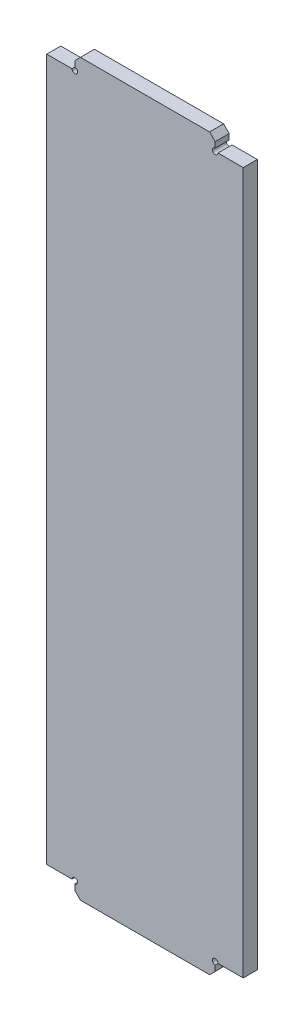
SolidWorks part; units mm, degrees
ref_plane "前基準面" through (0, 0, 0) normal (0, 0, 1) x (1, 0, 0)
ref_plane "上基準面" through (0, 0, 0) normal (0, 1, 0) x (1, 0, 0)
ref_plane "右基準面" through (0, 0, 0) normal (1, 0, 0) x (0, 0, -1)
sketch "草圖1" plane through (0, 0, 0) normal (0, 0, 1) x (1, 0, 0)
  line L0 (-25, 2) -> (-23, 0)
  line L3 (-23, 0) -> (23, 0)
  line L5 (23, 0) -> (25, 2)
  line L6 (-25, 2) -> (-25, 4)
  line L10 (-35, 5) -> (-35, 255)
  line L14 (35, 5) -> (35, 255)
  line L15 (-26, 5) -> (-35, 5)
  line L16 (25, 2) -> (25, 4)
  line L17 (26, 5) -> (35, 5)
  line L18 (-35, 130) -> (35, 130) construction
  line L19 (26, 255) -> (35, 255)
  line L20 (25, 258) -> (25, 256)
  line L21 (-26, 255) -> (-35, 255)
  line L22 (-25, 258) -> (-25, 256)
  line L23 (23, 260) -> (25, 258)
  line L24 (-23, 260) -> (23, 260)
  line L25 (-25, 258) -> (-23, 260)
  arc A0 (-25, 4) -> (-26, 5) centre (-25, 5) ccw
  arc A1 (26, 5) -> (25, 4) centre (25, 5) ccw
  arc A2 (26, 255) -> (25, 256) centre (25, 255) cw
  arc A3 (-25, 256) -> (-26, 255) centre (-25, 255) cw
  point P1 (25, 0)
  point P2 (-25, 0)
  point P8 (0, 0)
  point P30 (-25, 260)
  point P31 (25, 260)
  point P32 (0, 0)
  point P33 (0, 0)
  dimension "D8" = 1
  dimension "D1" = 50
  dimension "D2" = 70
  dimension "D3" = 250
  dimension "D7" = 3
extrude "填料-伸長1" add sketch "草圖1" along normal mid plane 5 contours L10 L21 A3 L22 L25 L24 L23 L20 A2 L19 L14 L17 A1 L16 L5 L3 L0 L6 A0 L15
